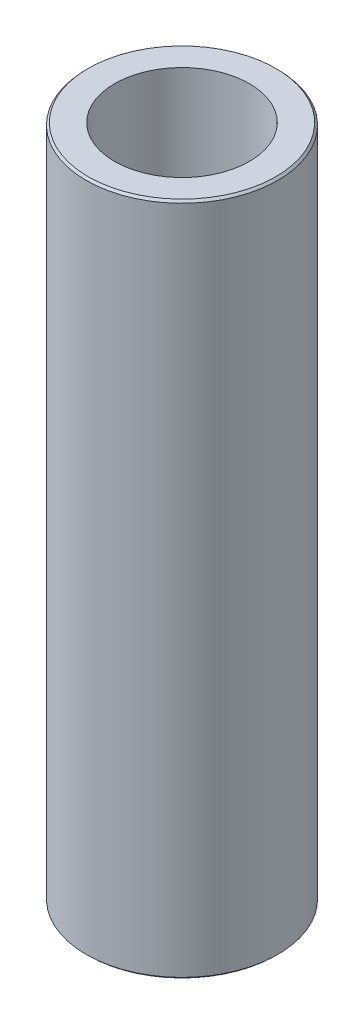
SolidWorks part; units mm, degrees
ref_plane "Front Plane" through (0, 0, 0) normal (0, 0, 1) x (1, 0, 0)
ref_plane "Top Plane" through (0, 0, 0) normal (0, 1, 0) x (1, 0, 0)
ref_plane "Right Plane" through (0, 0, 0) normal (1, 0, 0) x (0, 0, -1)
sketch "Sketch1" plane through (0, 0, 0) normal (0, 1, 0) x (1, 0, 0)
  circle A0 centre (0, 0) radius 50
  dimension "SHAFT_OD" = 100
extrude "Boss-Extrude1" add sketch "Sketch1" along normal blind 351.8673
sketch "Sketch2" plane through (0, 0, 0) normal (0, 1, 0) x (1, 0, 0)
  circle A0 centre (0, 0) radius 35.1685
  dimension "BORE_D" = 70.337
extrude "Cut-Extrude1" cut sketch "Sketch2" along normal through all
chamfer "Chamfer1" distance 1.1242 angle 43.341 2 edges at (0, 351.8673, 50) (0, 0, 50) first distance on face at (0, 351.8673, 50) first distance on face at (0, 0, 35.1685)
